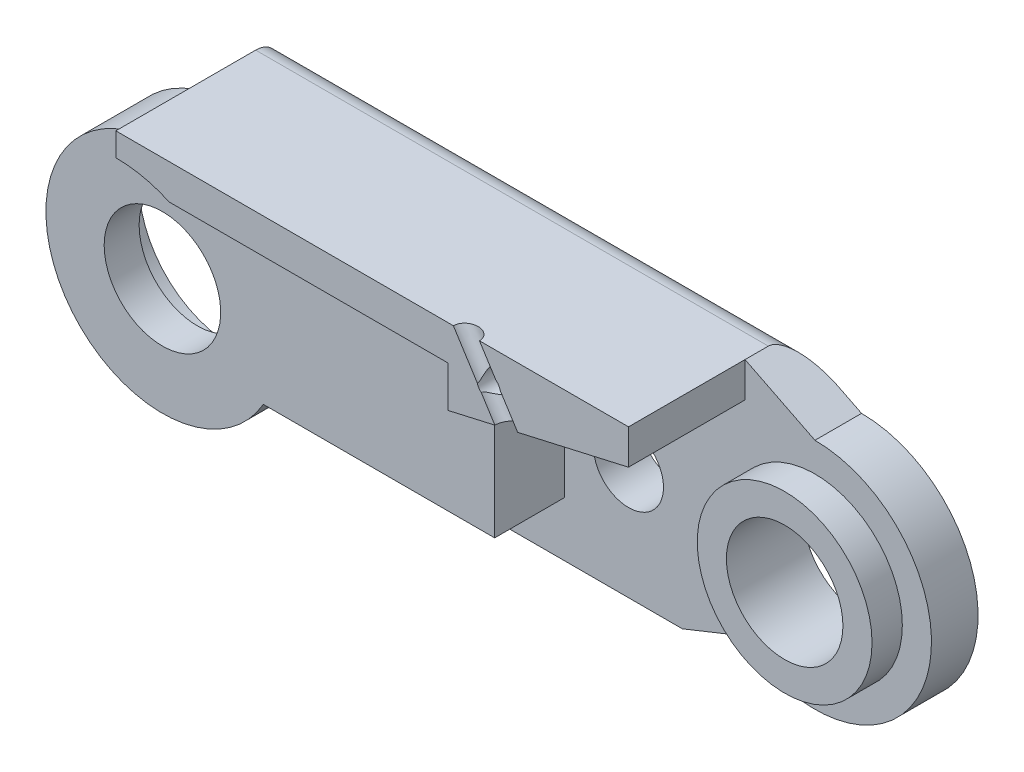
SolidWorks part; units mm, degrees
ref_plane "Front Plane" through (0, 0, 0) normal (0, 0, 1) x (1, 0, 0)
ref_plane "Top Plane" through (0, 0, 0) normal (0, 1, 0) x (1, 0, 0)
ref_plane "Right Plane" through (0, 0, 0) normal (1, 0, 0) x (0, 0, -1)
sketch "Sketch3" plane through (0, 0, 0) normal (0, 0, 1) x (1, 0, 0)
  line L0 (0, 5) -> (-2.5, 6) construction
  line L1 (-2.5, 6) -> (-20.5, 6) construction
  line L4 (-5.5, -5) -> (-3, -4) construction
  line L5 (0, 5.5) -> (0, 6.5)
  line L6 (0, 6.5) -> (22, 6.5)
  line L7 (5.5, 0) -> (6.5, -2.5)
  line L8 (6.5, -2.5) -> (6.5, -4.8513)
  line L9 (6.5, -4.8513) -> (19.3114, -4.8513)
  line L11 (25, 5) -> (22, 6.5)
  line L12 (21.8114, -3.8513) -> (19.3114, -4.8513)
  arc A1 (-3, -4) -> (0, 5) centre (0, 0) ccw construction
  arc A4 (5.5, 0) -> (0, 5.5) centre (0, 0) ccw
  arc A5 (21.8114, -3.8513) -> (25, 5) centre (25, 0) ccw
  dimension "D1" = 10
  dimension "D3" = 1
  dimension "D10" = 11
  dimension "D13" = 0
  dimension "D17" = 10
  dimension "D2" = 18
  dimension "D4" = 6
  dimension "D5" = 11
  dimension "D6" = 2.5
  dimension "D7" = 2.5
  dimension "D8" = 1
  dimension "D9" = 2.5
  dimension "D11" = 1
  dimension "D12" = 25
  dimension "D14" = 3
  dimension "D15" = 1
  dimension "D16" = 2.5
extrude "Boss-Extrude1" add sketch "Sketch3" along normal blind 2 contours A5 L11 L6 L5 A4 L7 L8 L9 L12
sketch "Sketch4" plane through (0, 0, 2) normal (0, 0, 1) x (1, 0, 0)
  line L0 (0, 6.5) -> (22, 6.5)
  line L1 (22, 6.5) -> (22, 5)
  line L2 (22, 5) -> (2.2913, 5)
  line L3 (0, 6.5) -> (0, 5.5)
  arc A0 (5.5, 0) -> (0, 5.5) centre (0, 0) ccw construction
  arc A1 (2.2913, 5) -> (0, 5.5) centre (0, 0) ccw
  dimension "D1" = 1.5
extrude "Boss-Extrude2" add sketch "Sketch4" along normal blind 5
sketch "Sketch5" plane through (0, 0, 0) normal (0, 0, 1) x (1, 0, 0)
  line L0 (0, 5) -> (-2.5, 6) construction
  line L1 (-2.5, 6) -> (-20.5, 6) construction
  line L4 (-5.5, -5) -> (-3, -4) construction
  arc A1 (-3, -4) -> (0, 5) centre (0, 0) ccw construction
  circle A6 centre (0, 0) radius 2.5 construction
  dimension "D1" = 10
  dimension "D3" = 1
  dimension "D2" = 18
  dimension "D4" = 6
  dimension "D5" = 11
  dimension "D6" = 2.5
  dimension "D7" = 2.5
sketch "Sketch6" plane through (0, 0, 2) normal (0, 0, 1) x (1, 0, 0)
  line L2 (2.2913, 5) -> (12.1456, 5)
  line L3 (2.2913, 5) -> (22, 5) construction
  line L6 (0, 5) -> (0, 5.5)
  line L7 (6.5, -2.5) -> (4.3301, -2.5)
  line L9 (12.1456, -2.5) -> (6.5, -2.5)
  line L10 (12.1456, 5) -> (14.2559, 5)
  line L11 (2.2913, 5) -> (22, 5) construction
  line L12 (14.2559, 5) -> (14.2559, -2.5)
  line L13 (14.2559, -2.5) -> (12.1456, -2.5)
  arc A1 (0, 5) -> (4.3301, -2.5) centre (0, 0) ccw
  arc A2 (0, 5.5) -> (2.2913, 5) centre (0, 0) cw
  arc A3 (5.5, 0) -> (2.2913, 5) centre (0, 0) ccw construction
extrude "Boss-Extrude3" add sketch "Sketch6" along normal blind 3 contours A1 L7 L9 L13 L12 L10 L2 A2 L6
sketch "Sketch7" plane through (0, 0, 2) normal (0, 0, -1) x (-1, 0, 0)
  circle A0 centre (0, 0) radius 2.5
extrude "Cut-Extrude1" cut sketch "Sketch7" against normal blind 3
sketch "Sketch8" plane through (0, 0, 2) normal (0, 0, -1) x (-1, 0, 0)
  circle A1 centre (0, 0) radius 4
  dimension "D1" = 8
extrude "Cut-Extrude2" cut sketch "Sketch8" against normal blind 1.5
sketch "Sketch9" plane through (0, 0, 5) normal (0, 0, 1) x (1, 0, 0)
  circle A0 centre (0, 0) radius 4
sketch "Sketch11" plane through (0, 0, 0) normal (0, 0, -1) x (-1, 0, 0)
  circle A0 centre (-25, 0) radius 2.7579 construction
sketch "Sketch12" plane through (0, 0, 2) normal (0, 0, 1) x (1, 0, 0)
  circle A0 centre (25, 0) radius 3.75
  dimension "D1" = 7.5
extrude "Boss-Extrude5" add sketch "Sketch12" along normal blind 1.3
sketch "Sketch13" plane through (0, 0, 0) normal (0, 0, -1) x (-1, 0, 0)
  circle A0 centre (-25, 0) radius 2.5
extrude "Cut-Extrude4" cut sketch "Sketch13" against normal through all
fillet "Fillet2" radius 1 2 edges at (12.9057, -4.8513, 0) (11, 6.5, 0)
sketch "Sketch14" plane through (0, 0, 0) normal (0, 0, -1) x (-1, 0, 0)
  circle A0 centre (-17, 0) radius 1.5
  dimension "D1" = 8
extrude "Cut-Extrude5" cut sketch "Sketch14" against normal blind 10
sketch "Sketch16" plane through (0, 0, 2) normal (0, 0, 1) x (1, 0, 0)
  line L0 (14.2559, 5) -> (14.2559, 3.2373)
  line L1 (14.2559, 5) -> (14.2559, -2.5) construction
  line L2 (14.2559, 3.2373) -> (22, 5)
  line L3 (22, 5) -> (14.2559, 5)
extrude "Boss-Extrude6" add sketch "Sketch16" along normal blind 5
sketch "Sketch17" plane through (0, 0, 7) normal (0, 0, 1) x (1, 0, 0)
  line L0 (22, 6.5) -> (0, 6.5) construction
  line L1 (22, 5) -> (22, 6.5) construction
  circle A0 centre (16, 5) radius 0.5
  dimension "D1" = 1.5
  dimension "D2" = 6
extrude "Cut-Extrude6" cut sketch "Sketch17" against normal through all
sketch "Sketch18" plane through (0, 0, 7) normal (0, 0, 1) x (1, 0, 0)
  line L0 (16, 5) -> (22.1863, -4.7489) construction
sketch "Sketch19" plane through (0.0016, -0.0072, 0) normal (0.2219, -0.9751, 0) x (0.9751, 0.2219, 0)
  line L0 (14.6188, 7) -> (22.561, 7) construction
  circle A0 centre (17.1812, 7) radius 0.5017
extrude "Cut-Extrude7" cut sketch "Sketch19" along direction (0.5358, -0.8444, 0) on the side against the normal blind 5
